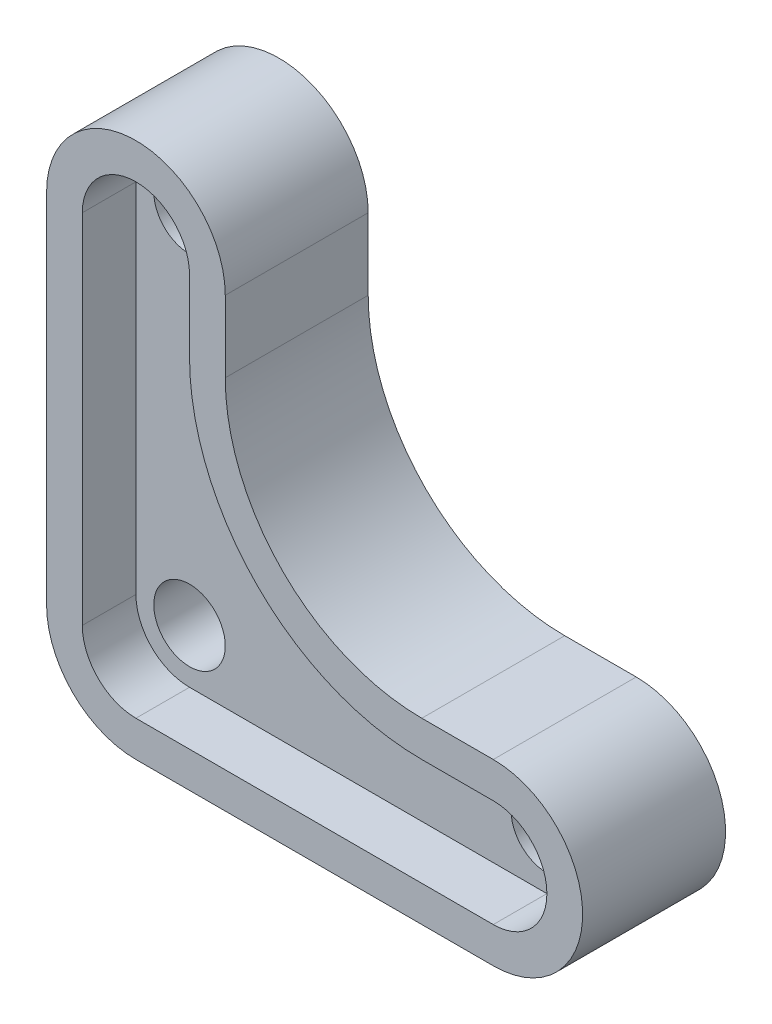
SolidWorks part; units mm, degrees
ref_plane "Front Plane" through (0, 0, 0) normal (0, 0, 1) x (1, 0, 0)
ref_plane "Top Plane" through (0, 0, 0) normal (0, 1, 0) x (1, 0, 0)
ref_plane "Right Plane" through (0, 0, 0) normal (1, 0, 0) x (0, 0, -1)
ref_plane "Plane1" through (0, 0, 13) normal (0, 0, 1) x (1, 0, 0)
sketch "Sketch1" plane through (0, 0, 13) normal (0, 0, 1) x (1, 0, 0)
  line L0 (-15, 5) -> (-15, 20)
  line L1 (-25, 20) -> (-25, -5)
  line L2 (-25, -5) -> (0, -5)
  line L3 (0, 5) -> (-15, 5)
  arc A0 (-15, 20) -> (-25, 20) centre (-20, 20) ccw
  arc A1 (0, -5) -> (0, 5) centre (0, 0) ccw
  dimension "D2" = 5
  dimension "D1" = 25
extrude "Boss-Extrude1" add sketch "Sketch1" against normal blind 8
sketch "Sketch2" plane through (0, 0, 13) normal (0, 0, 1) x (1, 0, 0)
  line L0 (-23, 20) -> (-23, -3)
  line L1 (-23, -3) -> (0, -3)
  line L2 (0, 3) -> (-17, 3)
  line L3 (-17, 3) -> (-17, 20)
  line L4 (-25, 20) -> (-25, -5) construction
  line L5 (-25, -5) -> (0, -5) construction
  arc A0 (0, -3) -> (0, 3) centre (0, 0) ccw
  arc A1 (-17, 20) -> (-23, 20) centre (-20, 20) ccw
  arc A2 (0, -5) -> (0, 5) centre (0, 0) ccw construction
  arc A3 (-15, 20) -> (-25, 20) centre (-20, 20) ccw construction
  dimension "D1" = 2
  dimension "D2" = 2
extrude "Cut-Extrude1" cut sketch "Sketch2" against normal blind 3
hole_wizard "Ø4.0 (4) Diameter Hole1" positions "Sketch4" profile "Sketch3" hole size "Ø4.0" standard "ANSI Metric"
sketch "Sketch4" plane through (0, 0, 5) normal (0, 0, -1) x (-1, 0, 0)
  arc A0 (25, 20) -> (15, 20) centre (20, 20) ccw construction
  point P0 (20, 20)
  point P1 (20, 0)
  point P2 (0, 0)
sketch "Sketch3" plane through (-20, 20, 5) normal (1, 0, 0) x (0, 1, 0)
  line L0 (0, 0) -> (0, 8)
  line L1 (0, 8) -> (2, 8)
  line L2 (2, 8) -> (2, 0)
  line L5 (2, 0) -> (0, 0)
  line L11 (0, -6.35) -> (0, 107.95) construction
  dimension "Thru Hole Dia." = 4
  dimension "Thru Hole Depth" = 8
fillet "Fillet1" radius 3 1 edges at (-23, -3, 11.5) tangent propagation no
fillet "Fillet2" radius 5 1 edges at (-25, -5, 9) tangent propagation no
fillet "Fillet3" radius 11 1 edges at (-15, 5, 9) tangent propagation no
fillet "Fillet4" radius 13 1 edges at (-17, 3, 11.5) tangent propagation no
ref_axis "Axis1" through (-20, 20, 10) along (0, 0, -1)
ref_axis "Axis2" through (-20, 0, 10) along (0, 0, -1)
ref_axis "Axis3" through (0, 0, 10) along (0, 0, -1)
